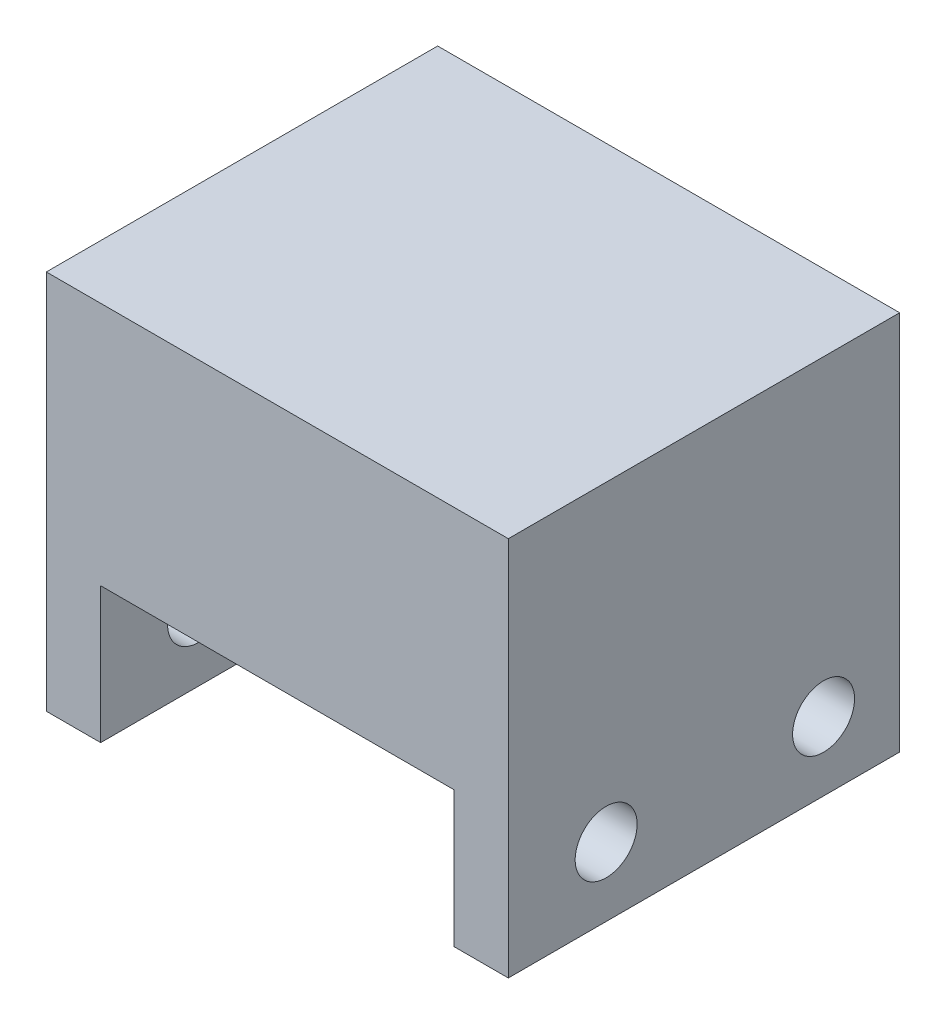
SolidWorks part; units mm, degrees
ref_plane "Alzado" through (0, 0, 0) normal (0, 0, 1) x (1, 0, 0)
ref_plane "Planta" through (0, 0, 0) normal (0, 1, 0) x (1, 0, 0)
ref_plane "Vista lateral" through (0, 0, 0) normal (1, 0, 0) x (0, 0, -1)
sketch "Croquis1" plane through (0, 0, 0) normal (0, 1, 0) x (1, 0, 0)
  line L1 (-27.9362, 52.1383) -> (-112.9362, 52.1383)
  line L2 (-27.9362, 52.1383) -> (-27.9362, -19.8617)
  line L3 (-27.9362, -19.8617) -> (-112.9362, -19.8617)
  line L4 (-112.9362, 52.1383) -> (-112.9362, -19.8617)
  dimension "D1" = 85
  dimension "D2" = 72
extrude "Saliente-Extruir1" add sketch "Croquis1" along normal blind 70
sketch "Croquis3" plane through (0, 0, 0) normal (0, 1, 0) x (1, 0, 0)
  line L0 (-27.9362, -19.8617) -> (-27.9362, 52.1383) construction
  line L1 (-102.9362, 52.1383) -> (-37.9362, 52.1383)
  line L2 (-102.9362, 52.1383) -> (-102.9362, -19.8617)
  line L3 (-102.9362, -19.8617) -> (-37.9362, -19.8617)
  line L4 (-37.9362, 52.1383) -> (-37.9362, -19.8617)
  line L5 (-112.9362, 52.1383) -> (-112.9362, -19.8617) construction
  point P8 (0, 0)
  dimension "D1" = 10
  dimension "D2" = 10
  dimension "D3" = 72
extrude "Cortar-Extruir2" cut sketch "Croquis3" along normal blind 25 contours L2 L1 L4 L3
sketch "Croquis5" plane through (-27.9362, 0, 0) normal (1, 0, 0) x (0, 0, -1)
  line L1 (52.1383, 70) -> (52.1383, 0) construction
  circle A0 centre (-1.8617, 12.6656) radius 5.7
  circle A1 centre (38.1383, 12.6656) radius 5.7
  point P4 (38.6387, 12.6656)
  point P7 (0, 0)
  point P8 (0, 0)
  point P9 (31.9741, 4.192)
  dimension "D1" = 40
  dimension "D3" = 14
extrude "Cortar-Extruir3" cut sketch "Croquis5" against normal up to vertex (85 mm away) up to point (-112.9362, 0, 19.8617)
shell "Vaciado1" thickness 10 removed face at (-70.4362, 25, -16.1383)
